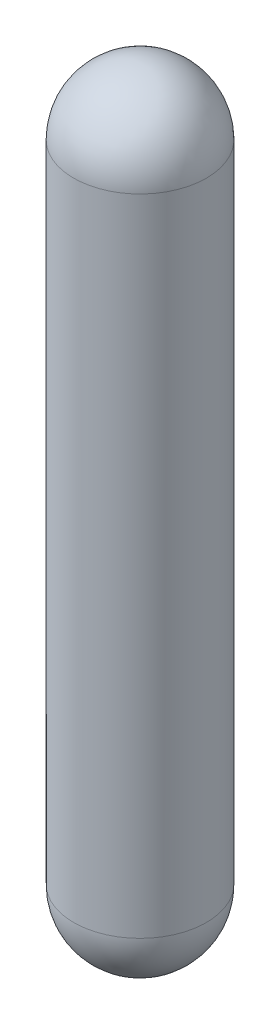
SolidWorks part; units mm, degrees
other "Markup1"
sketch "Sketch2" plane through (-160, -160, 160) normal (0, 0, 1) x (1, 0, 0)
ref_plane "Front Plane" through (0, 0, 0) normal (0, 0, 1) x (1, 0, 0)
ref_plane "Top Plane" through (0, 0, 0) normal (0, 1, 0) x (1, 0, 0)
ref_plane "Right Plane" through (0, 0, 0) normal (1, 0, 0) x (0, 0, -1)
sketch "Sketch1" plane through (0, 0, 0) normal (0, 0, 1) x (1, 0, 0)
  line L0 (0, 1990) -> (0, 2195)
  line L2 (0, 0) -> (0, 1990)
  line L4 (205, 0) -> (205, 1990)
  line L5 (0, 0) -> (0, -205)
  line L6 (0, 738.4774) -> (205, 738.4774) construction
  arc A0 (0, -205) -> (205, 0) centre (0, 0) ccw
  arc A1 (205, 1990) -> (0, 2195) centre (0, 1990) ccw
  dimension "D1" = 205
  dimension "D2" = 2400
revolve "Revolve1" add sketch "Sketch1" angle 360 about L2
